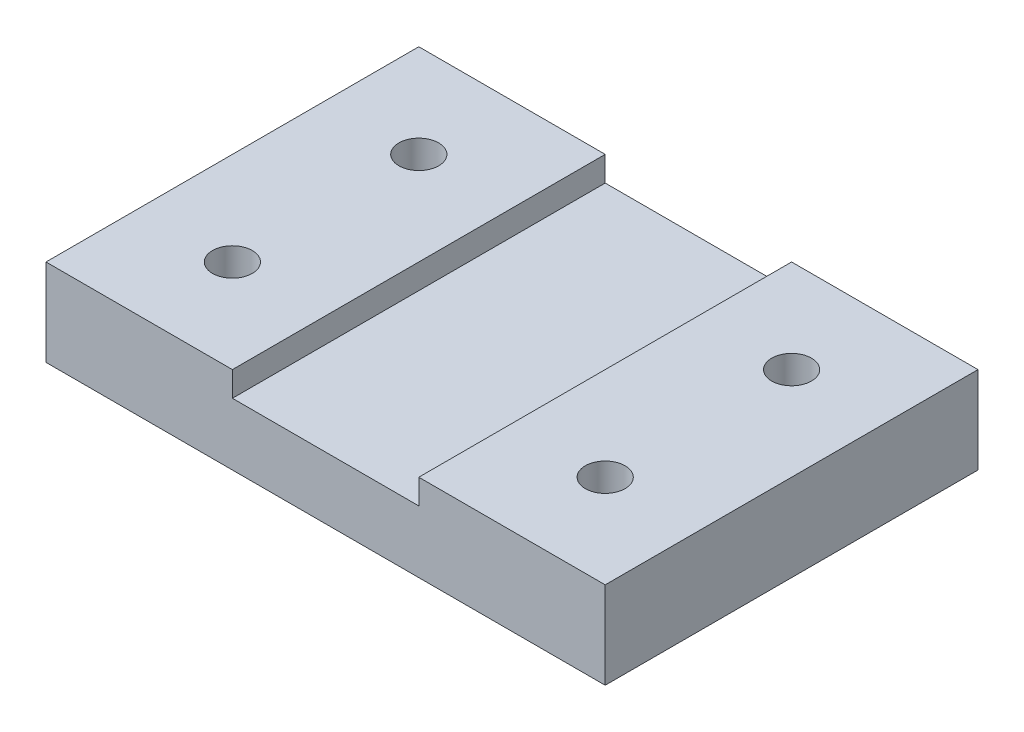
SolidWorks part; units mm, degrees
ref_plane "Front Plane" through (0, 0, 0) normal (0, 0, 1) x (1, 0, 0)
ref_plane "Top Plane" through (0, 0, 0) normal (0, 1, 0) x (1, 0, 0)
ref_plane "Right Plane" through (0, 0, 0) normal (1, 0, 0) x (0, 0, -1)
sketch "Sketch1" plane through (0, 0, 0) normal (0, 1, 0) x (1, 0, 0)
  line L0 (-22.5, 15) -> (-7.5, 0) construction
  line L1 (-7.5, -15) -> (7.5, -15)
  line L2 (-7.5, -15) -> (-7.5, 15)
  line L3 (-7.5, 15) -> (7.5, 15)
  line L4 (7.5, -15) -> (7.5, 15)
  line L5 (-7.5, -15) -> (7.5, 15) construction
  line L6 (-7.5, 15) -> (7.5, -15) construction
  line L7 (-7.5, 15) -> (-22.5, 15)
  line L8 (-7.5, 15) -> (-7.5, -15)
  line L9 (-7.5, -15) -> (-22.5, -15)
  line L10 (-22.5, 15) -> (-22.5, -15)
  line L11 (7.5, 15) -> (22.5, 15)
  line L12 (7.5, 15) -> (7.5, -15)
  line L13 (7.5, -15) -> (22.5, -15)
  line L14 (22.5, 15) -> (22.5, -15)
  line L15 (-7.5, 0) -> (-22.5, -15) construction
  line L16 (22.5, 15) -> (7.5, 0) construction
  line L17 (7.5, 0) -> (22.5, -15) construction
  circle A0 centre (-15, 7.5) radius 1.6
  circle A1 centre (15, 7.5) radius 1.6
  circle A2 centre (-15, -7.5) radius 1.6
  circle A3 centre (15, -7.5) radius 1.6
  point P0 (0, 0)
  dimension "D5" = 3.2
  dimension "D6" = 3.2
  dimension "D7" = 3.2
  dimension "D8" = 3.2
  dimension "D1" = 30
  dimension "D2" = 15
  dimension "D3" = 15
  dimension "D4" = 15
extrude "Boss-Extrude1" add sketch "Sketch1" along normal blind 7 contours L7 L10 L9 L2 A2 A0 | L14 L11 L4 L13 A3 A1 region at (-15, 0, 0) region at (15, 0, 0)
extrude "Boss-Extrude2" add sketch "Sketch1<3>" along normal blind 5 contours L1 L4 L3 L2 region at (0, 0, 0)
sketch "Sketch1<3>" plane through (0, 0, 0) normal (0, 1, 0) x (1, 0, 0) same geometry as "Sketch1"
